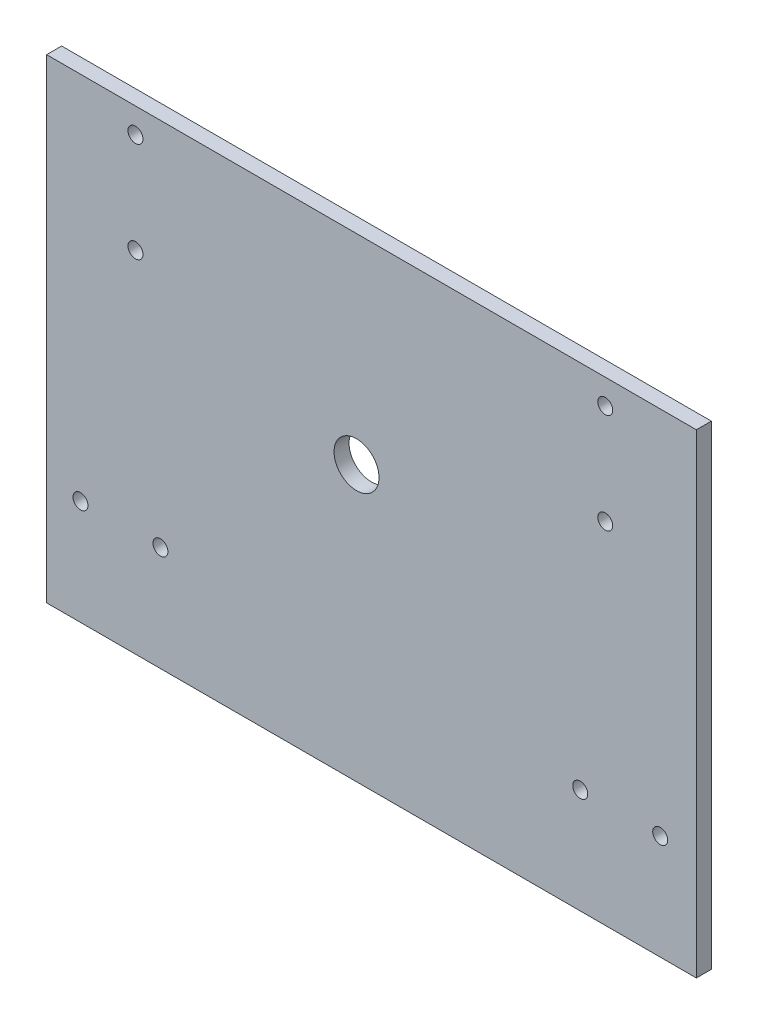
SolidWorks part; units mm, degrees
ref_plane "前视基准面" through (0, 0, 0) normal (0, 0, 1) x (1, 0, 0)
ref_plane "上视基准面" through (0, 0, 0) normal (0, 1, 0) x (1, 0, 0)
ref_plane "右视基准面" through (0, 0, 0) normal (1, 0, 0) x (0, 0, -1)
sketch "草图1" plane through (0, 0, 0) normal (0, 0, 1) x (1, 0, 0)
  line L1 (65, -47.5) -> (-65, -47.5)
  line L2 (65, -47.5) -> (65, 47.5)
  line L3 (65, 47.5) -> (-65, 47.5)
  line L4 (-65, -47.5) -> (-65, 47.5)
  line L5 (65, -47.5) -> (-65, 47.5) construction
  line L6 (65, 47.5) -> (-65, -47.5) construction
  point P0 (0, 0)
  dimension "D1" = 130
  dimension "D2" = 95
extrude "凸台-拉伸1" add sketch "草图1" along normal blind 3
sketch "草图2" plane through (0, 0, 3) normal (0, 0, 1) x (1, 0, 0)
  line L0 (0, -47.5) -> (0, -26.5) construction
  line L1 (-65, -47.5) -> (65, -47.5) construction
  line L2 (0, -26.5) -> (10, -26.5) construction
  circle A0 centre (10, -26.5) radius 1.5
  circle A1 centre (-10, -26.5) radius 1.5
  dimension "D3" = 3
  dimension "D1" = 21
  dimension "D2" = 10
sketch "草图3" plane through (0, 0, 0) normal (0, 0, -1) x (-1, 0, 0)
  circle A0 centre (-57.7671, -26.5) radius 1.5
  circle A1 centre (-41.7671, -26.5) radius 1.5
  circle A2 centre (42.2329, -26.5) radius 1.5
  circle A4 centre (58.2329, -26.5) radius 1.5
extrude "切除-拉伸2" cut sketch "草图3" against normal blind 10
sketch "草图4" plane through (0, 0, 0) normal (0, 0, -1) x (-1, 0, 0)
  circle A0 centre (-46.7671, 42.5) radius 1.5
  circle A1 centre (-46.7671, 22.5) radius 1.5
  circle A2 centre (47.2329, 42.5) radius 1.5
  circle A3 centre (47.2329, 22.5) radius 1.5
extrude "切除-拉伸3" cut sketch "草图4" against normal blind 10
sketch "草图9" plane through (0, 0, 3) normal (0, 0, 1) x (1, 0, 0)
  circle A0 centre (-3, 7.4526) radius 4.5
  dimension "D1" = 9
extrude "切除-拉伸4" cut sketch "草图9" against normal blind 10
